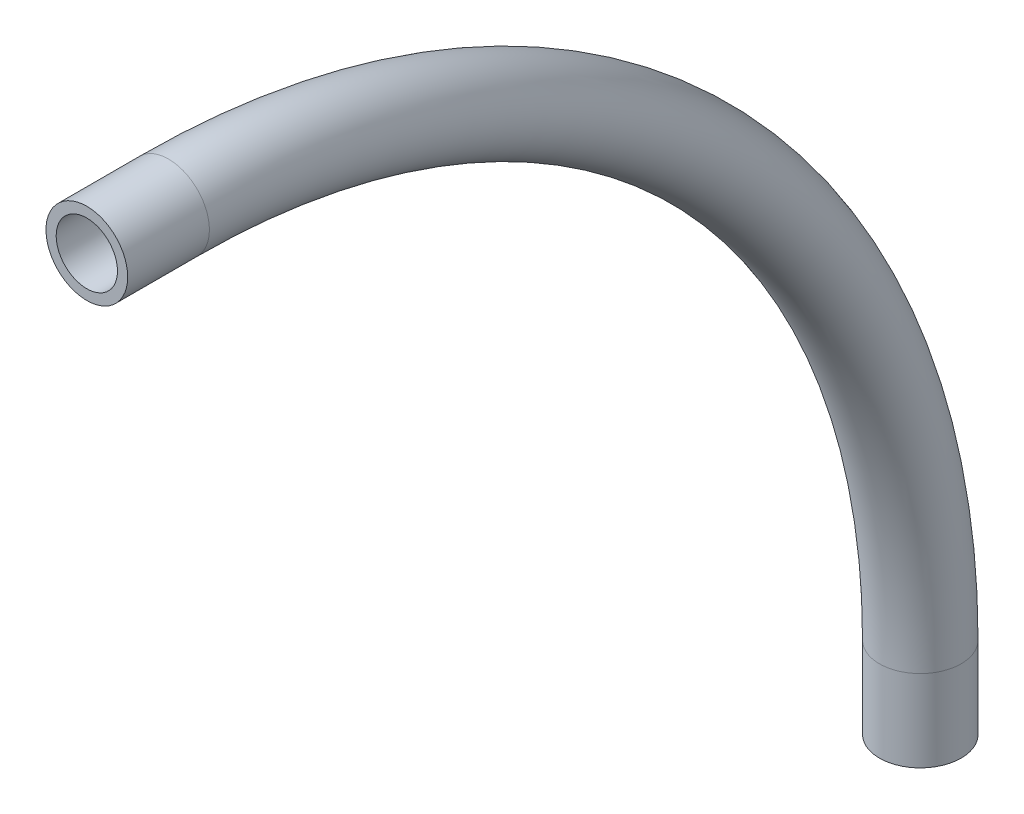
SolidWorks part; units mm, degrees
material "Acrylic (Medium-high impact)"
ref_plane "Front" through (0, 0, 0) normal (0, 0, 1) x (1, 0, 0)
ref_plane "Top" through (0, 0, 0) normal (0, 1, 0) x (1, 0, 0)
ref_plane "Right" through (0, 0, 0) normal (1, 0, 0) x (0, 0, -1)
sketch "Sketch1" plane through (0, 0, 0) normal (0, 0, 1) x (1, 0, 0)
  circle A0 centre (0, 0) radius 4.7625
  circle A1 centre (0, 0) radius 6.35
  dimension "D1" = 12.7
  dimension "D2" = 9.525
sketch "Sketch2" plane through (0, 0, 0) normal (1, 0, 0) x (0, 0, -1)
  line L0 (0, 0) -> (12.7, 0)
  line L1 (0, 4.7625) -> (0, -4.7625) construction
  line L2 (129.54, -116.84) -> (129.54, -129.54)
  arc A0 (12.7, 0) -> (129.54, -116.84) centre (12.7, -116.84) cw
  dimension "D1" = 90
  dimension "D2" = 12.7
  dimension "D3" = 116.84
sweep "Sweep1" add profiles "Sketch1" path "Sketch2"
